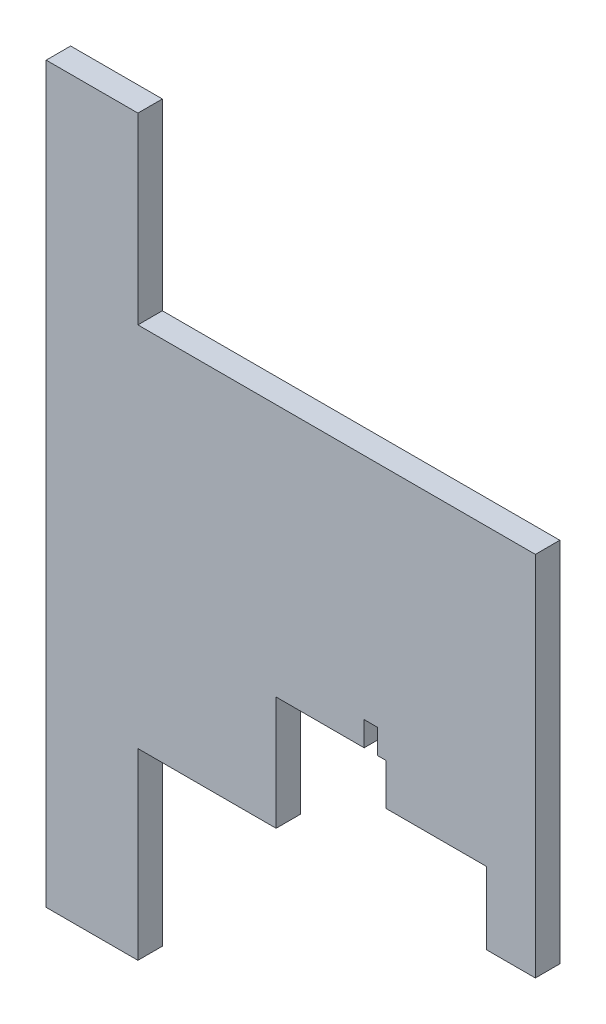
SolidWorks part; units mm, degrees
material "Beech"
ref_plane "Front Plane" through (0, 0, 0) normal (0, 0, 1) x (1, 0, 0)
ref_plane "Top Plane" through (0, 0, 0) normal (0, 1, 0) x (1, 0, 0)
ref_plane "Right Plane" through (0, 0, 0) normal (1, 0, 0) x (0, 0, -1)
sketch "Sketch1" plane through (0, 0, 0) normal (0, 0, 1) x (1, 0, 0)
  line L0 (0, 0) -> (82.55, 0)
  line L1 (82.55, 0) -> (82.55, -76.2)
  line L2 (82.55, -76.2) -> (0, -76.2)
  line L3 (0, 0) -> (0, 38.1)
  line L4 (0, 38.1) -> (-19.05, 38.1)
  line L5 (-19.05, 38.1) -> (-19.05, -114.3)
  line L6 (-19.05, -114.3) -> (0, -114.3)
  line L7 (0, -114.3) -> (0, -76.2)
  dimension "D1" = 82.55
  dimension "D2" = 76.2
  dimension "D3" = 152.4
  dimension "D4" = 38.1
  dimension "D5" = 19.05
extrude "Boss-Extrude1" add sketch "Sketch1" along normal blind 5.08
sketch "Sketch2" plane through (0, 0, 5.08) normal (0, 0, 1) x (1, 0, 0)
  line L0 (28.702, -76.2) -> (28.702, -52.578)
  line L1 (0, -76.2) -> (82.55, -76.2) construction
  line L2 (28.702, -52.578) -> (46.99, -52.578)
  line L3 (46.99, -52.578) -> (46.99, -47.498)
  line L4 (46.99, -47.498) -> (49.784, -47.498)
  line L5 (49.784, -47.498) -> (49.784, -52.578)
  line L6 (49.784, -52.578) -> (51.562, -52.578)
  line L8 (72.39, -61.214) -> (72.39, -76.2)
  line L9 (28.702, -76.2) -> (72.39, -76.2)
  line L10 (82.55, -76.2) -> (82.55, 0) construction
  line L11 (51.562, -52.578) -> (51.562, -61.214)
  line L12 (51.562, -61.214) -> (72.39, -61.214)
  dimension "D1" = 30.988
  dimension "D2" = 20.828
  dimension "D3" = 2.794
  dimension "D4" = 5.08
  dimension "D5" = 18.288
  dimension "D6" = 14.986
  dimension "D7" = 1.778
  dimension "D8" = 8.636
extrude "Cut-Extrude1" cut sketch "Sketch2" against normal through all both and the other way through all contours L2 L3 L4 L5 L6 L11 L12 L8 L9 L0
